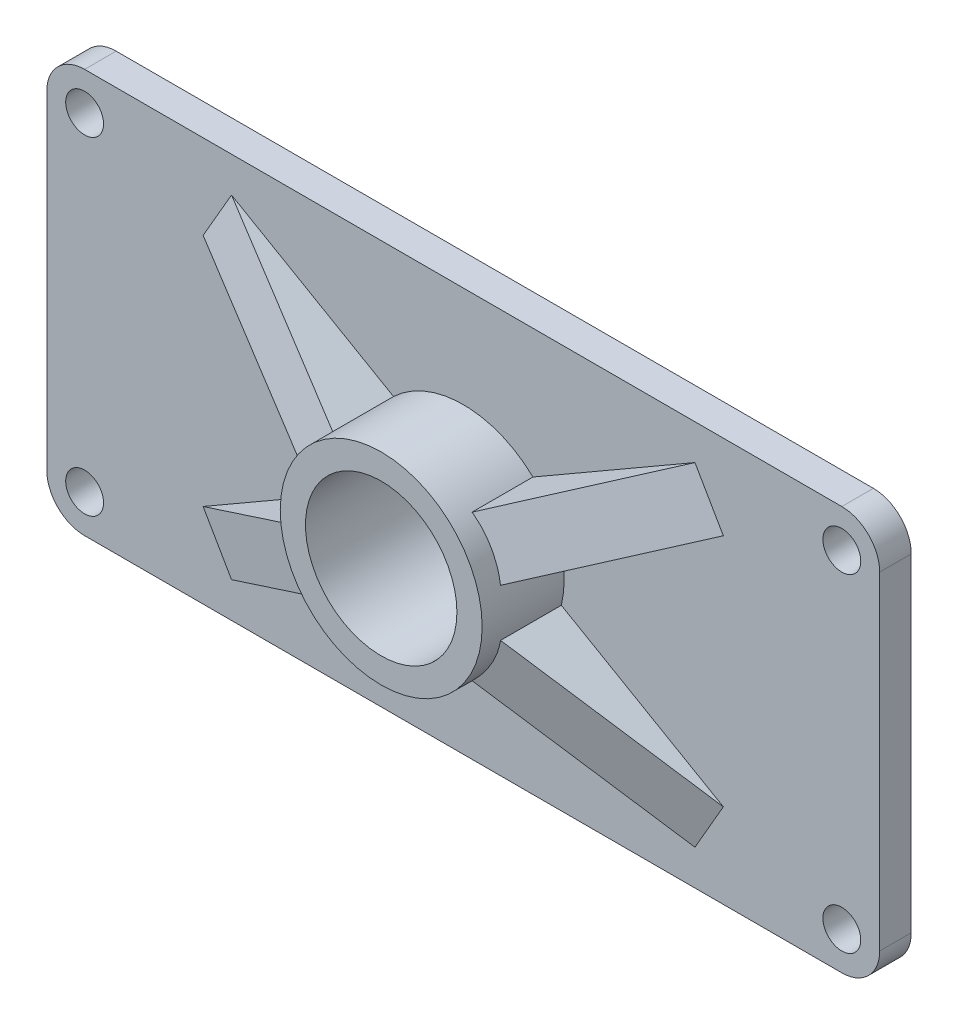
SolidWorks part; units mm, degrees
material "Thornel Mat VMA"
ref_plane "Front Plane" through (0, 0, 0) normal (0, 0, 1) x (1, 0, 0)
ref_plane "Top Plane" through (0, 0, 0) normal (0, 1, 0) x (1, 0, 0)
ref_plane "Right Plane" through (0, 0, 0) normal (1, 0, 0) x (0, 0, -1)
sketch "Sketch3" plane through (0, 0, 0) normal (0, 0, 1) x (1, 0, 0)
  line L1 (-60, 32) -> (60, 32)
  line L2 (-66, 26) -> (-66, -26)
  line L3 (-60, -32) -> (60, -32)
  line L4 (66, 26) -> (66, -26)
  line L5 (-66, 32) -> (66, -32) construction
  line L6 (-66, -32) -> (66, 32) construction
  arc A0 (60, -32) -> (66, -26) centre (60, -26) ccw
  arc A1 (-66, -26) -> (-60, -32) centre (-60, -26) ccw
  arc A2 (60, 32) -> (66, 26) centre (60, 26) cw
  arc A3 (-60, 32) -> (-66, 26) centre (-60, 26) ccw
  circle A4 centre (-60, 26) radius 3
  circle A5 centre (60, 26) radius 3
  circle A6 centre (60, -26) radius 3
  circle A7 centre (-60, -26) radius 3
  circle A8 centre (0, 0) radius 12
  circle A9 centre (0, 0) radius 16
  point P0 (0, 0)
  dimension "D3" = 6
  dimension "D4" = 6
  dimension "D5" = 6
  dimension "D6" = 6
  dimension "D7" = 6
  dimension "D8" = 24
  dimension "D11" = 32
  dimension "D1" = 132
  dimension "D2" = 64
  dimension "D9" = 32
  dimension "D10" = 66
extrude "Base PLate" add sketch "Sketch3" along normal blind 5 contours L1 A3 L2 A1 L3 A0 L4 A2 A9 A7 A6 A5 A4 region at (0, 30.533, 0)
extrude "Middle Bump" add sketch "Sketch3<3>" along normal blind 18 contours A9 A8 region at (-15.5475, 0, 0)
sketch "Sketch3<3>" plane through (0, 0, 0) normal (0, 0, 1) x (1, 0, 0) same geometry as "Sketch3"
ref_plane "Plane1" through (0, 0, 0) normal (-0.5, 0.866, 0) x (0, 0, -1)
sketch "Sketch4" plane through (0, 0, 0) normal (-0.5, 0.866, 0) x (0, 0, -1)
  line L6 (-14.4227, 16) -> (-5, 45)
  line L7 (-5, 16) -> (-18, 16) construction
  line L8 (-5, 44.1577) -> (-5, 70.1577) construction
  line L9 (-18, 0) -> (0, 0) construction
  dimension "D1" = 45
  dimension "D2" = 162
rib "Rib3" sketch "Sketch4" sketch "Sketch4" thickness 9 extrusion direction parallel to sketch draft on no parameters "D1"=9
mirror "Mirror4" about plane through (0, 0, 0) normal (1, 0, 0) of "Rib3"
mirror "Mirror5" about plane through (0, 0, 0) normal (0, 1, 0) of "Mirror4"
